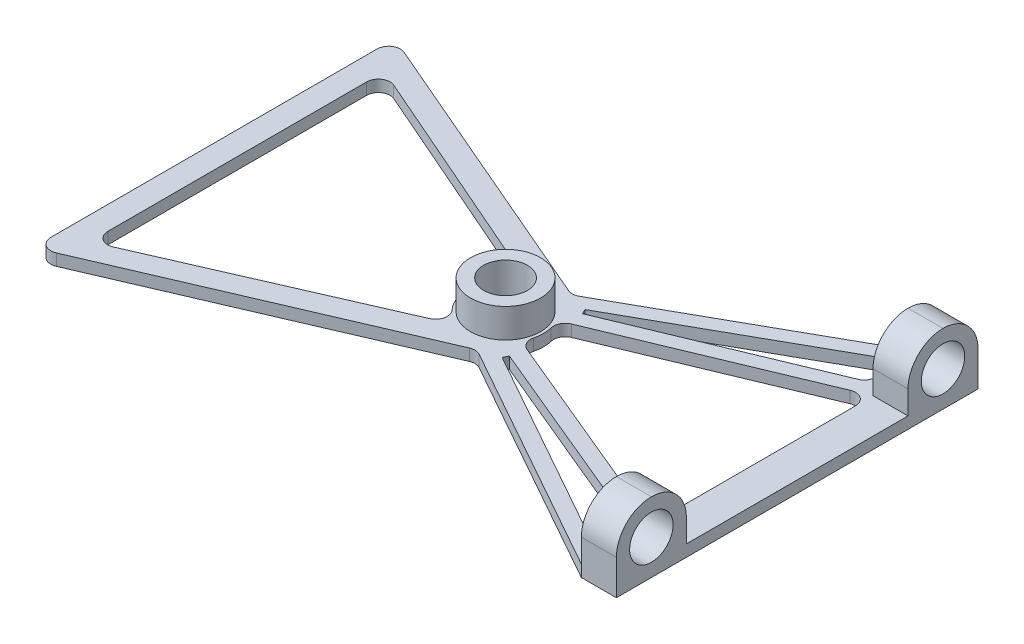
SolidWorks part; units mm, degrees
ref_plane "Front" through (0, 0, 0) normal (0, 0, 1) x (1, 0, 0)
ref_plane "Top" through (0, 0, 0) normal (0, 1, 0) x (1, 0, 0)
ref_plane "Right" through (0, 0, 0) normal (1, 0, 0) x (0, 0, -1)
sketch "草图1" plane through (0, 0, 0) normal (0, 1, 0) x (1, 0, 0)
  line L1 (0, 0) -> (100, 0)
  line L2 (0, 0) -> (0, -100)
  line L3 (0, -100) -> (100, -100)
  line L4 (100, 0) -> (100, -100)
  dimension "D1" = 100
  dimension "D2" = 100
extrude "凸台-拉伸1" add sketch "草图1" along normal blind 2
sketch "草图2" plane through (0, 2, 0) normal (0, 1, 0) x (1, 0, 0)
  line L0 (100, -100) -> (100, 0) construction
  line L1 (100, -19) -> (94, -19)
  line L2 (100, -19) -> (100, -31)
  line L3 (100, -31) -> (94, -31)
  line L4 (94, -19) -> (94, -31)
  line L5 (100, 0) -> (0, 0) construction
  line L6 (111, -50) -> (0, -50) construction
  line L8 (100, -81) -> (100, -69)
  line L9 (100, -81) -> (94, -81)
  line L10 (94, -81) -> (94, -69)
  line L11 (100, -69) -> (94, -69)
  dimension "D1" = 6
  dimension "D2" = 12
  dimension "D3" = 19
extrude "凸台-拉伸2" add sketch "草图2" along normal blind 10
sketch "草图3" plane through (100, 0, 0) normal (1, 0, 0) x (0, 0, -1)
  line L0 (-81, 12) -> (-69, 12) construction
  line L1 (-69, 12) -> (-69, 2) construction
  line L2 (-31, 12) -> (-19, 12) construction
  line L3 (-19, 12) -> (-19, 2) construction
  circle A0 centre (-25, 6) radius 3.725
  circle A1 centre (-75, 6) radius 3.725
  dimension "D5" = 7.45
  dimension "D6" = 7.45
  dimension "D1" = 6
  dimension "D2" = 6
  dimension "D3" = 6
  dimension "D4" = 6
extrude "切除-拉伸1" cut sketch "草图3" against normal through all
sketch "草图4" plane through (0, 2, 0) normal (0, 1, 0) x (1, 0, 0)
  line L0 (100, 0) -> (0, 0) construction
  line L1 (100, -69) -> (100, -31) construction
  circle A0 centre (50, -50) radius 6
  dimension "D3" = 12
  dimension "D1" = 50
  dimension "D2" = 50
extrude "凸台-拉伸3" add sketch "草图4" along normal blind 5
sketch "草图5" plane through (0, 7, 0) normal (0, 1, 0) x (1, 0, 0)
  circle A0 centre (50, -50) radius 3.75
  dimension "D1" = 7.5
extrude "切除-拉伸2" cut sketch "草图5" against normal through all
sketch "草图6" plane through (0, 2, 0) normal (0, 1, 0) x (1, 0, 0)
  line L1 (100, -81) -> (0, -81)
  line L2 (100, -81) -> (100, -100)
  line L3 (100, -100) -> (0, -100)
  line L4 (0, -81) -> (0, -100)
  line L5 (100, -19) -> (0, -19)
  line L6 (100, -19) -> (100, 0)
  line L7 (100, 0) -> (0, 0)
  line L8 (0, -19) -> (0, 0)
extrude "切除-拉伸3" cut sketch "草图6" against normal through all
sketch "草图7" plane through (0, 2, 0) normal (0, 1, 0) x (1, 0, 0)
  line L0 (94, -69) -> (94, -31)
  line L1 (94, -31) -> (55.2674, -47.1269)
  line L2 (55.2674, -52.8731) -> (94, -69)
  line L3 (55.2674, -47.1269) -> (0, -23)
  line L4 (0, -19) -> (0, -81) construction
  line L5 (55.2674, -52.8731) -> (0, -77)
  line L6 (0, -19) -> (94, -19) construction
  line L7 (94, -81) -> (0, -81) construction
  line L8 (94, -19) -> (48.852, -44.3263)
  line L9 (94, -81) -> (48.852, -55.6737)
  line L10 (0, -81) -> (53.2128, -58.1199)
  line L11 (0, -19) -> (53.2128, -41.8801)
  line L12 (94, -31) -> (94, -69)
  line L13 (100, -69) -> (100, -31)
  line L14 (100, -31) -> (94, -31)
  line L15 (4, -75.2538) -> (4, -24.7462)
  line L16 (94, -19) -> (0, -19)
  line L17 (94, -81) -> (0, -81)
  circle A0 centre (50, -50) radius 6 construction
  circle A1 centre (50, -50) radius 6.5
  line M1 (94, -19) -> (0, -19)
  line M3 (0, -81) -> (94, -81)
  dimension "D7" = 13
  dimension "D1" = 4
  dimension "D2" = 4
  dimension "D3" = 7
  dimension "D4" = 7
  dimension "D5" = 5
  dimension "D6" = 5
  dimension "D8" = 4
extrude "切除-拉伸4" cut sketch "草图7" against normal through all contours A1 L2 L0 L1 | L11 L8 M1 | A1 L3 L15 L5 | L10 L9 M3 region at (79.5598, 2, 50) region at (49.0709, 2, 73.3733) region at (49.0709, 2, 26.6267) region at (20.7484, 2, 50)
fillet "圆角1" radius 6 4 edges at (97, 12, 81) (97, 12, 69) (97, 12, 31) (97, 12, 19)
sketch "草图8" plane through (0, 2, 0) normal (0, 1, 0) x (1, 0, 0)
  line L0 (94, -31) -> (55.7313, -46.9337)
  line L1 (55.7313, -53.0663) -> (94, -69)
  line L2 (55.7313, -53.0663) -> (94, -69) construction
  line L3 (94, -69) -> (94, -81)
  line L4 (94, -81) -> (53.2128, -58.1199)
  line L5 (91.5, -76.7311) -> (56.5122, -57.1043)
  line L6 (55.7313, -46.9337) -> (53.2128, -41.8801)
  line L7 (55.7313, -53.0663) -> (53.2128, -58.1199)
  line L8 (56.9269, -56.2721) -> (56.5122, -57.1043)
  line L9 (56.9269, -56.2721) -> (91.5, -70.6671)
  line L10 (91.5, -70.6671) -> (91.5, -76.7311)
  line L11 (91.5, -29.3329) -> (56.9269, -43.7279)
  line L12 (56.9269, -43.7279) -> (56.5122, -42.8957)
  line L13 (56.5122, -42.8957) -> (91.5, -23.2689)
  line L14 (53.2128, -41.8801) -> (94, -19)
  line L15 (94, -19) -> (94, -31)
  line L16 (91.5, -23.2689) -> (91.5, -29.3329)
  line L17 (94, -31) -> (55.7313, -46.9337) construction
  arc A0 (55.7313, -53.0663) -> (55.7313, -46.9337) centre (50, -50) ccw construction
  dimension "D1" = 2.5
  dimension "D2" = 2.5
extrude "切除-拉伸6" cut sketch "草图8" against normal through all contours L16 L13 L12 L11 | L10 L9 L8 L5 region at (78.2159, 2, 67.208) region at (78.2159, 2, 32.792)
fillet "圆角2" radius 2 4 edges at (55.7313, 1, 53.0663) (55.7313, 1, 46.9337) (47.8209, 1, 43.8761) (47.8209, 1, 56.1239)
fillet "圆角3" radius 2 12 edges at (94, 1, 69) (94, 1, 31) (53.2128, 1, 41.8801) (53.2128, 1, 58.1199) (91.5, 1, 76.7311) (91.5, 1, 70.6671) (91.5, 1, 29.3329) (91.5, 1, 23.2689) (0, 1, 19) (0, 1, 81) (4, 1, 75.2538) (4, 1, 24.7462)
